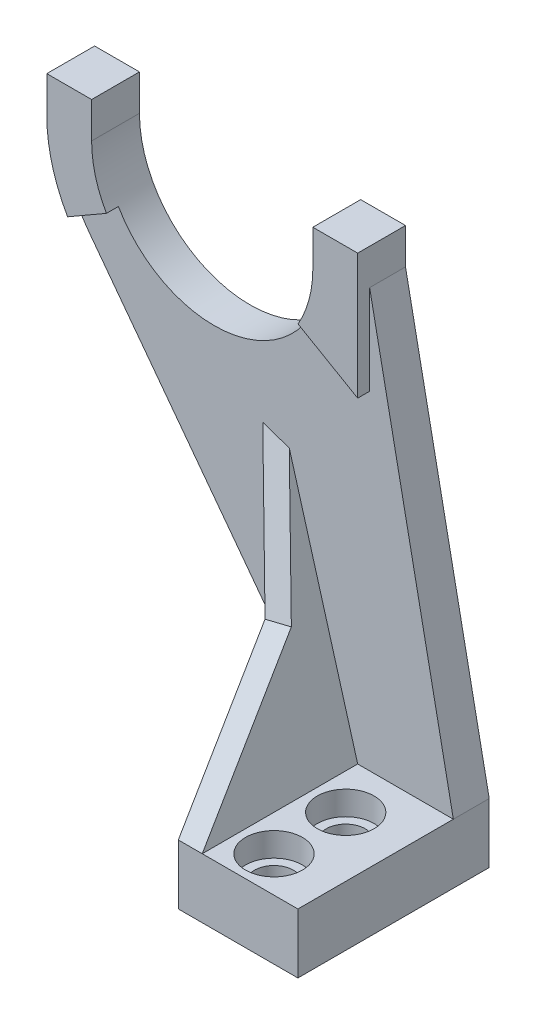
SolidWorks part; units mm, degrees
ref_plane "Front Plane" through (0, 0, 0) normal (0, 0, 1) x (1, 0, 0)
ref_plane "Top Plane" through (0, 0, 0) normal (0, 1, 0) x (1, 0, 0)
ref_plane "Right Plane" through (0, 0, 0) normal (1, 0, 0) x (0, 0, -1)
sketch "Sketch1" plane through (0, 0, 0) normal (0, 0, 1) x (1, 0, 0)
  line L0 (0, 0) -> (31.75, 0)
  line L1 (31.75, 0) -> (31.75, 15.875)
  line L2 (0, 0) -> (0, 15.875)
  line L3 (0, 15.875) -> (-64.77, 102.235)
  line L4 (-73.025, 127) -> (-61.1188, 127) construction
  line L5 (-2.3813, 127) -> (9.525, 127) construction
  line L6 (-73.025, 127) -> (-73.025, 136.525)
  line L7 (-73.025, 136.525) -> (-61.1188, 136.525)
  line L8 (-61.1188, 136.525) -> (-61.1188, 127)
  line L9 (-2.3813, 127) -> (-2.3813, 136.525)
  line L10 (-2.3813, 136.525) -> (9.525, 136.525)
  line L11 (9.525, 136.525) -> (9.525, 127)
  line L12 (9.525, 127) -> (9.525, 15.875)
  line L13 (9.525, 15.875) -> (31.75, 15.875)
  line L14 (-31.75, 127) -> (-67.4952, 106.3625)
  line L15 (-31.75, 127) -> (9.525, 103.1699)
  arc A0 (-73.025, 127) -> (-64.77, 102.235) centre (-31.75, 127) ccw
  arc A1 (-61.1188, 127) -> (-2.3813, 127) centre (-31.75, 127) ccw
  dimension "D2" = 82.55
  dimension "D6" = 58.7375
  dimension "D1" = 15.875
  dimension "D3" = 127
  dimension "D4" = 63.5
  dimension "D5" = 31.75
  dimension "D7" = 9.525
  dimension "D8" = 30
  dimension "D9" = 30
extrude "Boss-Extrude1" add sketch "Sketch1" along normal blind 9.525 contours A1 L8 L7 L6 A0 L3 L2 L0 L1 L13 L12 L11 L10 L9 | A1 L8 L7 L6 A0 L14 | A1 L15 L12 L11 L10 L9 region at (-12.233, 64.0892, 0) region at (-66.2319, 122.5969, 0) region at (3.3492, 121.1086, 0)
ref_plane "Plane1" through (0, 0, 4.7625) normal (0, 0, 1) x (1, 0, 0)
sketch "Sketch3" plane through (0, 0, 4.7625) normal (0, 0, 1) x (1, 0, 0)
  line L0 (31.75, 15.875) -> (9.525, 127)
  line L1 (9.525, 136.525) -> (9.525, 15.875) construction
  dimension "D1" = 9.525
rib "Rib1" sketch "Sketch3" sketch "Sketch3" thickness 9.525 extrusion direction parallel to sketch draft on no parameters "D1"=9.525
extrude "Boss-Extrude2" add sketch "Sketch1<3>" along normal blind 12.7 contours A1 L8 L7 L6 A0 L14 | A1 L15 L12 L11 L10 L9 region at (-66.2319, 122.5969, 0) region at (3.3492, 121.1086, 0)
sketch "Sketch1<3>" plane through (0, 0, 0) normal (0, 0, 1) x (1, 0, 0) same geometry as "Sketch1"
sketch "Sketch4" plane through (0, 0, 9.525) normal (0, 0, 1) x (1, 0, 0)
  line L1 (0, 0) -> (31.75, 0)
  line L2 (0, 0) -> (0, 15.875)
  line L3 (0, 15.875) -> (31.75, 15.875)
  line L4 (31.75, 0) -> (31.75, 15.875)
extrude "Boss-Extrude3" add sketch "Sketch4" along normal blind 41.275
sketch "Sketch6" plane through (0, 0, 9.525) normal (0, 0, 1) x (1, 0, 0)
  line L0 (-31.75, 127) -> (0, 15.875) construction
  line L1 (-31.75, 127) -> (-25.6443, 128.7445) construction
  line L2 (0, 15.875) -> (6.1057, 17.6195) construction
  arc A0 (-57.1841, 112.3156) -> (-6.3159, 112.3156) centre (-31.75, 127) ccw construction
  point P4 (-18.8509, 81.8532)
  dimension "D1" = 17.5846
  dimension "D2" = 6.35
  dimension "D3" = 6.35
ref_axis "Axis1" through (-31.75, 127, 9.525) along (0.2587, -0.9055, 0.3363)
ref_plane "Plane3" through (4.1934, 1.1981, 0) normal (0.9615, 0.2747, 0) x (0, 0, -1)
sketch "Sketch10" plane through (4.1934, 1.1981, 0) normal (0.9615, 0.2747, 0) x (0, 0, -1)
  line L0 (-50.8, -8.7224) -> (-50.8, 6.5418) construction
  line L1 (-9.525, 83.8826) -> (-50.8, 83.8826)
  line L2 (-9.525, 83.8826) -> (-9.525, 15.2642)
  line L3 (-9.525, 15.2642) -> (-50.8, 15.2642)
  line L4 (-50.8, 83.8826) -> (-50.8, 15.2642)
  line L5 (-50.8, 15.2642) -> (-9.525, 15.2642) construction
extrude "Boss-Extrude4" add sketch "Sketch10" along direction (-1, 0, 0) on the side of the normal blind 6.35
sketch "Sketch11" plane through (10.0642, 2.8755, 0) normal (0.9615, 0.2747, 0) x (0, 0, -1)
  line L0 (-50.8, 13.5197) -> (-19.05, 45.2697)
  line L2 (-9.525, 82.1381) -> (-50.8, 82.1381)
  line L3 (-50.8, 82.1381) -> (-50.8, 13.5197)
  line L4 (-9.525, 13.5197) -> (-9.525, 82.1381) construction
  line L5 (-50.8, 13.5197) -> (-9.525, 13.5197) construction
  line L6 (-19.05, 45.2697) -> (-9.525, 54.7947)
  line M5 (-50.8, 82.1381) -> (-50.8, 13.5197)
  line M7 (-9.525, 13.5197) -> (-9.525, 82.1381)
  line M8 (-9.525, 82.1381) -> (-50.8, 82.1381)
  dimension "D1" = 9.525
  dimension "D2" = 31.75
extrude "Cut-Extrude5" cut sketch "Sketch11" along direction (-1, 0, 0) on the side against the normal through all contours L0 L6 M7 M8 M5 region at (-5.5038, 57.3633, 33.1214)
sketch "Sketch12" plane through (4.1934, 1.1981, 0) normal (0.9615, 0.2747, 0) x (0, 0, -1)
  line L0 (-19.05, 47.0142) -> (-9.525, 83.8826)
  line L1 (-9.525, 56.5392) -> (-50.8, 15.2642) construction
  line L2 (-9.525, 6.5418) -> (-9.525, 119.4968) construction
  line L3 (-9.525, 13.5197) -> (-9.525, 54.7947) construction
  line L4 (-19.05, 47.0142) -> (-9.525, 56.5392)
  line L5 (-9.525, 56.5392) -> (-9.525, 83.8826)
  dimension "D1" = 9.525
  dimension "D2" = 17.5846
ref_plane "Plane4" through (10.0642, 2.8755, 0) normal (0.9615, 0.2747, 0) x (0, 0, -1)
sketch "Sketch13" plane through (10.0642, 2.8755, 0) normal (0.9615, 0.2747, 0) x (0, 0, -1)
  line L3 (-18.1778, 46.142) -> (-8.6528, 83.0103)
  line L4 (-9.525, 54.7947) -> (-8.6528, 83.0103)
  line L5 (-18.1778, 46.142) -> (-9.525, 54.7947)
  line L8 (-50.8, 13.5197) -> (-9.525, 54.7947) construction
loft "Loft2" add profiles "Sketch13", "Sketch12" connector at (-12.7405, 82.6919, 8.6528) connector at (-18.8509, 81.8532, 9.525)
sketch "Sketch14" plane through (0, 15.875, 0) normal (0, 1, 0) x (1, 0, 0)
  line L0 (31.75, -50.8) -> (31.75, -9.525) construction
  line L1 (31.75, -50.8) -> (6.35, -50.8) construction
  circle A0 centre (15.875, -41.275) radius 7.5406
  circle A1 centre (15.875, -22.225) radius 7.5406
  dimension "D2" = 15.0812
  dimension "D1" = 19.05
  dimension "D3" = 15.875
  dimension "D4" = 9.525
extrude "Cut-Extrude6" cut sketch "Sketch14" against normal blind 6.35
sketch "Sketch15" plane through (0, 9.525, 0) normal (0, 1, 0) x (1, 0, 0)
  circle A0 centre (15.875, -22.225) radius 5.1594
  circle A1 centre (15.875, -41.275) radius 5.1594
  dimension "D1" = 10.3187
extrude "Cut-Extrude7" cut sketch "Sketch15" against normal through all
